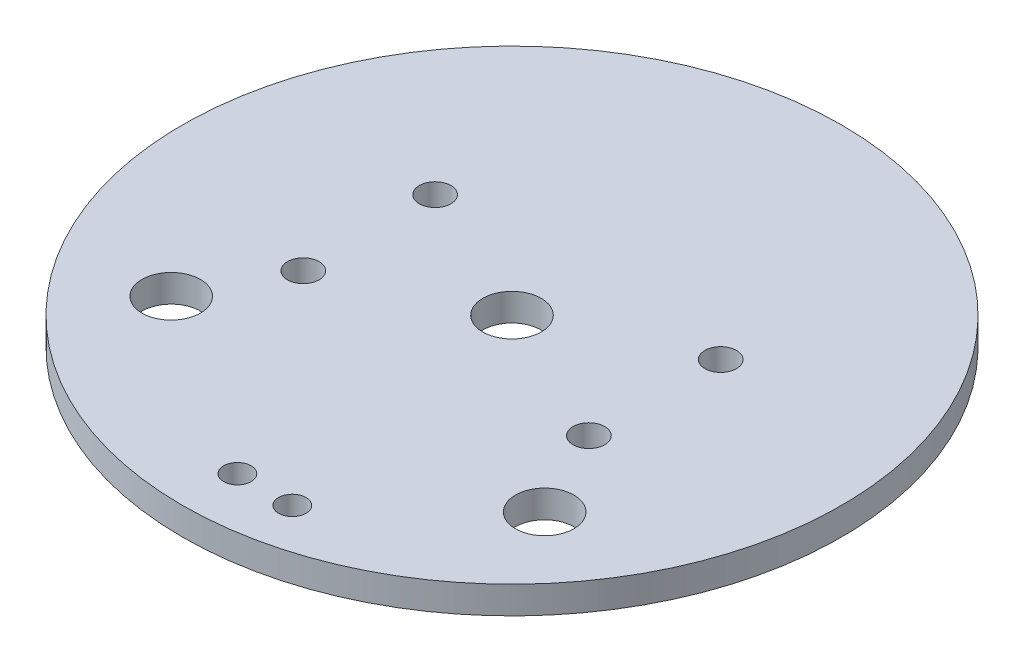
SolidWorks part; units mm, degrees
ref_plane "Front Plane" through (0, 0, 0) normal (0, 0, 1) x (1, 0, 0)
ref_plane "Top Plane" through (0, 0, 0) normal (0, 1, 0) x (1, 0, 0)
ref_plane "Right Plane" through (0, 0, 0) normal (1, 0, 0) x (0, 0, -1)
sketch "Sketch1" plane through (0, 0, 0) normal (0, 1, 0) x (1, 0, 0)
  circle A0 centre (0, 0) radius 38.1
  dimension "D1" = 76.2
extrude "Boss-Extrude1" add sketch "Sketch1" along normal mid plane 3.175 contours A0
sketch "Sketch2" plane through (0, 0, 0) normal (0, 1, 0) x (1, 0, 0)
  line L0 (-35.9958, -12.4865) -> (35.9958, -12.4865)
  line L1 (-30.2719, -23.1349) -> (30.2719, -23.1349)
  line L2 (-21.59, -12.4865) -> (-21.59, -23.1349) construction
  line L3 (0, -1.7462) -> (0, 1.7462) construction
  line L6 (-1.7462, 0) -> (1.7462, 0) construction
  circle A0 centre (0, 0) radius 38.1 construction
  circle A2 centre (0, 0) radius 38.1
  circle A3 centre (0, 0) radius 38.1
  point P4 (0, -12.4865)
  point P8 (0, -23.1349)
  point P13 (-21.59, -17.8107)
  point P14 (0, -31.75)
  point P15 (21.59, -17.8107)
  point P23 (-16.51, 7.62)
  point P24 (16.51, 7.62)
  point P25 (-16.51, -7.62)
  point P26 (16.51, -7.62)
  dimension "D1" = 12.4865
  dimension "D2" = 23.1349
  dimension "D3" = 21.59
  dimension "D4" = 31.75
  dimension "D5" = 7.62
  dimension "D6" = 7.62
  dimension "D7" = 7.62
  dimension "D8" = 7.62
  dimension "D9" = 16.51
  dimension "D10" = 16.51
  dimension "D11" = 16.51
  dimension "D12" = 16.51
  dimension "D13" = 0
hole_wizard "1/4 Clearance Hole1" positions "Sketch3" profile "Sketch4" hole size "1/4" standard "ANSI Inch" end condition through all
sketch "Sketch3" plane through (0, 1.5875, 0) normal (0, 1, 0) x (1, 0, 0)
  point P0 (-21.59, -17.8107)
  point P3 (21.59, -17.8107)
sketch "Sketch4" plane through (-21.59, 1.5875, 17.8107) normal (1, 0, 0) x (0, 0, 1)
  line L0 (0, 0) -> (0, 3.175)
  line L1 (0, 3.175) -> (3.3782, 3.175)
  line L2 (3.3782, 3.175) -> (3.3782, 0)
  line L5 (3.3782, 0) -> (0, 0)
  line L11 (0, -6.35) -> (0, 107.95) construction
  dimension "Thru Hole Dia." = 6.7564
  dimension "Thru Hole Depth" = 3.175
hole_wizard "1/4 Clearance Hole2" positions "Sketch5" profile "Sketch6" hole size "1/4" standard "ANSI Inch" end condition through all
sketch "Sketch5" plane through (0, 1.5875, 0) normal (0, 1, 0) x (1, 0, 0)
  point P0 (0, 0)
sketch "Sketch6" plane through (0, 1.5875, 0) normal (1, 0, 0) x (0, 0, 1)
  line L0 (0, 0) -> (0, 3.175)
  line L1 (0, 3.175) -> (3.3782, 3.175)
  line L2 (3.3782, 3.175) -> (3.3782, 0)
  line L5 (3.3782, 0) -> (0, 0)
  line L11 (0, -6.35) -> (0, 107.95) construction
  dimension "Thru Hole Dia." = 6.7564
  dimension "Thru Hole Depth" = 3.175
hole_wizard "1/8 (0.125) Diameter Hole1" positions "Sketch7" profile "Sketch8" hole size "1/8" standard "ANSI Inch" end condition through all
sketch "Sketch7" plane through (0, 1.5875, 0) normal (0, 1, 0) x (1, 0, 0)
  line L0 (0, -1.7463) -> (0, 1.7463) construction
  point P0 (0, -31.75)
  point P3 (6.35, -31.75)
  dimension "D1" = 6.35
sketch "Sketch8" plane through (0, 1.5875, 31.75) normal (1, 0, 0) x (0, 0, 1)
  line L0 (0, 0) -> (0, 3.175)
  line L1 (0, 3.175) -> (1.5875, 3.175)
  line L2 (1.5875, 3.175) -> (1.5875, 0)
  line L5 (1.5875, 0) -> (0, 0)
  line L11 (0, -6.35) -> (0, 107.95) construction
  dimension "Thru Hole Dia." = 3.175
  dimension "Thru Hole Depth" = 3.175
hole_wizard "#27 (0.144) Diameter Hole1" positions "Sketch9" profile "Sketch10" hole size "#27" standard "ANSI Inch" end condition through all
sketch "Sketch9" plane through (0, 1.5875, 0) normal (0, 1, 0) x (1, 0, 0)
  point P0 (-16.51, 7.62)
  point P3 (16.51, 7.62)
  point P6 (16.51, -7.62)
  point P9 (-16.51, -7.62)
sketch "Sketch10" plane through (-16.51, 1.5875, -7.62) normal (1, 0, 0) x (0, 0, 1)
  line L0 (0, 0) -> (0, 3.175)
  line L1 (0, 3.175) -> (1.8288, 3.175)
  line L2 (1.8288, 3.175) -> (1.8288, 0)
  line L5 (1.8288, 0) -> (0, 0)
  line L11 (0, -6.35) -> (0, 107.95) construction
  dimension "Thru Hole Dia." = 3.6576
  dimension "Thru Hole Depth" = 3.175
equation "\"dia\"= 3in"
equation "\"D1@Sketch1\"=\"dia\""
